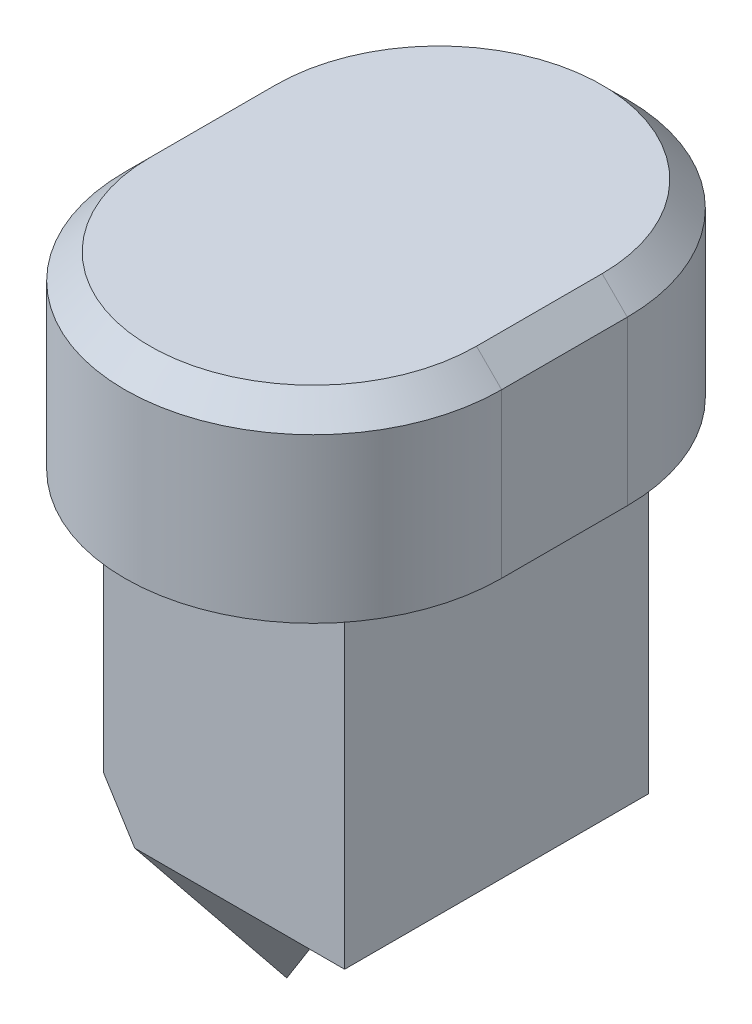
SolidWorks part; units mm, degrees
ref_plane "Front Plane" through (0, 0, 0) normal (0, 0, 1) x (1, 0, 0)
ref_plane "Top Plane" through (0, 0, 0) normal (0, 1, 0) x (1, 0, 0)
ref_plane "Right Plane" through (0, 0, 0) normal (1, 0, 0) x (0, 0, -1)
sketch "Sketch1" plane through (0, 0, 0) normal (0, 1, 0) x (1, 0, 0)
  line L1 (-9.6, 12.1) -> (9.6, 12.1)
  line L2 (-9.6, 12.1) -> (-9.6, -12.1)
  line L3 (-9.6, -12.1) -> (9.6, -12.1)
  line L4 (9.6, 12.1) -> (9.6, -12.1)
  line L5 (-9.6, 12.1) -> (9.6, -12.1) construction
  line L6 (-9.6, -12.1) -> (9.6, 12.1) construction
  point P0 (0, 0)
  dimension "D1" = 19.2
  dimension "D2" = 24.2
extrude "Boss-Extrude1" add sketch "Sketch1" along normal blind 26.1
sketch "Sketch2" plane through (0, 26.1, 0) normal (0, 1, 0) x (1, 0, 0)
  line L0 (0, 5) -> (0, -5) construction
  line L1 (15, 5) -> (15, -5)
  line L2 (-15, 5) -> (-15, -5)
  line L3 (0, 20) -> (0, -20) construction
  line L4 (-9.6, 0) -> (9.6, 0) construction
  line L5 (-9.6, 12.1) -> (-9.6, -12.1) construction
  line L6 (9.6, -12.1) -> (9.6, 12.1) construction
  arc A0 (15, 5) -> (-15, 5) centre (0, 5) ccw
  arc A1 (-15, -5) -> (15, -5) centre (0, -5) ccw
  point P3 (0, 0)
  dimension "D1" = 30
  dimension "D2" = 40
extrude "Boss-Extrude2" add sketch "Sketch2" along normal blind 15
sketch "Sketch4" plane through (-9.6, 0, 0) normal (-1, 0, 0) x (0, 0, 1)
  line L0 (0, 0) -> (0, -15) construction
  line L1 (-12.1, 0) -> (0, -15)
  line L2 (0, -15) -> (12.1, 0)
  line L3 (12.1, 0) -> (-12.1, 0)
  dimension "D1" = 15
extrude "Boss-Extrude3" add sketch "Sketch4" against normal blind 5
sketch "Sketch6" plane through (0, 0, 0) normal (0, 0, 1) x (1, 0, 0)
  line L0 (-4.6, -5) -> (9.6, 0)
  line L1 (-4.6, -15) -> (-4.6, 0) construction
  line L3 (-4.6, -5) -> (-4.6, 0)
  line L4 (-4.6, 0) -> (9.6, 0)
  dimension "D1" = 10
extrude "Boss-Extrude4" add sketch "Sketch6" along normal mid plane 3
chamfer "Chamfer1" distance 2.5 angle 45 4 edges at (-9.6, -7.5, -6.05) (-9.6, -7.5, 6.05) (-4.6, -7.5, -6.05) (-4.6, -7.5, 6.05)
fillet "Fillet1" radius 3 2 edges at (-4.6, 0, -5.194) (-4.6, 0, 5.194)
sketch "Sketch8" plane through (0, 0, 0) normal (1, 0, 0) x (0, 0, -1)
  line L0 (-81.3954, 120) -> (81.3954, 120) construction
  line L1 (-81.3954, 120) -> (81.3954, 120)
  line L2 (0, 120) -> (0, 38.6046) construction
  arc A0 (-81.3954, 120) -> (81.3954, 120) centre (0, 120) ccw
  dimension "D1" = 120
sketch "Sketch9" plane through (0, 26.1, 0) normal (0, -1, 0) x (1, 0, 0)
  line L4 (9.6, -12.1) -> (-9.6, -12.1) construction
  line L5 (-9.6, -12.1) -> (-9.6, 12.1) construction
  line L6 (-9.6, 12.1) -> (9.6, 12.1) construction
  line L7 (9.6, 12.1) -> (9.6, -12.1) construction
  line L8 (9.6, -12.1) -> (-9.6, -12.1)
  line L9 (-9.6, -12.1) -> (-9.6, 12.1)
  line L10 (-9.6, 12.1) -> (9.6, 12.1)
  line L11 (9.6, 12.1) -> (9.6, -12.1)
extrude "Cut-Extrude-Thin1" cut sketch "Sketch9" against normal blind 10 thin thin type one direction wall 0.3
sketch "Sketch10" plane through (-9.6, 0, 0) normal (-1, 0, 0) x (0, 0, 1)
  line L0 (-12.4, 36.1) -> (12.4, 36.1) construction
  line L1 (-12.4, 36.1) -> (12.4, 36.1)
  line L2 (-12.4, 36.1) -> (-12.4, 36.4)
  line L3 (-12.4, 36.4) -> (12.4, 36.4)
  line L4 (12.4, 36.1) -> (12.4, 36.4)
  line L5 (-12.4, 36.1) -> (-12.4, 26.1) construction
  dimension "D1" = 0.3
extrude "Cut-Extrude1" cut sketch "Sketch10" against normal up to surface (19.2 mm away) up to face at (9.6, 12.0333, 0)
sketch "Sketch12" plane through (0, 36.1, 0) normal (0, -1, 0) x (1, 0, 0)
  line L1 (-9.9, 12.4) -> (9.9, 12.4)
  line L2 (-9.9, 12.4) -> (-9.9, -12.4)
  line L3 (-9.9, -12.4) -> (9.9, -12.4)
  line L4 (9.9, 12.4) -> (9.9, -12.4)
extrude "Cut-Extrude3" cut sketch "Sketch12" against normal up to surface (0.3 mm away) up to face at (0, 36.4, 0)
chamfer "Chamfer2" distance 0.75 angle 45 4 edges at (0, 26.1, -12.4) (9.9, 26.1, 0) (0, 26.1, 12.4) (-9.9, 26.1, 0)
chamfer "Chamfer3" distance 0.75 angle 45 4 edges at (0, 36.1, -12.1) (-9.6, 36.1, 0) (0, 36.1, 12.1) (9.6, 36.1, 0)
sketch "Sketch14" plane through (0, 26.1, 0) normal (0, -1, 0) x (1, 0, 0)
  line L0 (0, 20) -> (0, 12.4) construction
  line L1 (9.9, 12.4) -> (-9.9, 12.4) construction
  line L2 (0, -20) -> (0, -12.4) construction
  line L3 (9.9, -12.4) -> (-9.9, -12.4) construction
  arc A0 (15, 5) -> (-15, 5) centre (0, 5) ccw construction
  circle A1 centre (0, -16.2) radius 2.2
  arc A2 (-15, -5) -> (15, -5) centre (0, -5) ccw construction
  circle A3 centre (0, 16.2) radius 2.2
  circle A4 centre (0, 16.2) radius 1.25
  circle A5 centre (0, -16.2) radius 1.25
  dimension "D1" = 4.4
  dimension "D2" = 4.4
  dimension "D3" = 2.5
  dimension "D4" = 2.5
extrude "Cut-Extrude4" cut sketch "Sketch14" against normal blind 4
chamfer "Chamfer6" distance 2 angle 45 4 edges at (-15, 41.1, 0) (0, 41.1, 20) (0, 41.1, -20) (15, 41.1, 0)
sketch "Sketch16" plane through (0, 26.1, 0) normal (0, -1, 0) x (1, 0, 0)
  circle A1 centre (0, 16.2) radius 1.25
  circle A2 centre (0, 16.2) radius 1.25
  circle A3 centre (0, -16.2) radius 1.25
  circle A4 centre (0, -16.2) radius 1.25
  dimension "D1" = 0
  dimension "D2" = 0
extrude "Cut-Extrude6" cut sketch "Sketch16" against normal blind 1
equation "\"Hole Length\"= 25"
equation "\"Hole Height\"= 20"
equation "\"Shell Thickness\"= 5"
equation "\"Can Diameter\"= 66.3"
equation "\"Hole Tolerance\"= 0.8"
equation "\"D1@Sketch1\"=\"Hole Height\"-\"Hole Tolerance\""
equation "\"D2@Sketch1\"=\"Hole Length\"-\"Hole Tolerance\""
equation "\"D1@Sketch2\"=\"Hole Height\"+10"
equation "\"D2@Sketch2\"=\"Hole Length\"+15"
equation "\"D1@Boss-Extrude1\"=\"Shell Thickness\"+21.1"
equation "\"Blade thickness\"= 5"
equation "\"D1@Boss-Extrude3\"=\"Blade thickness\""
